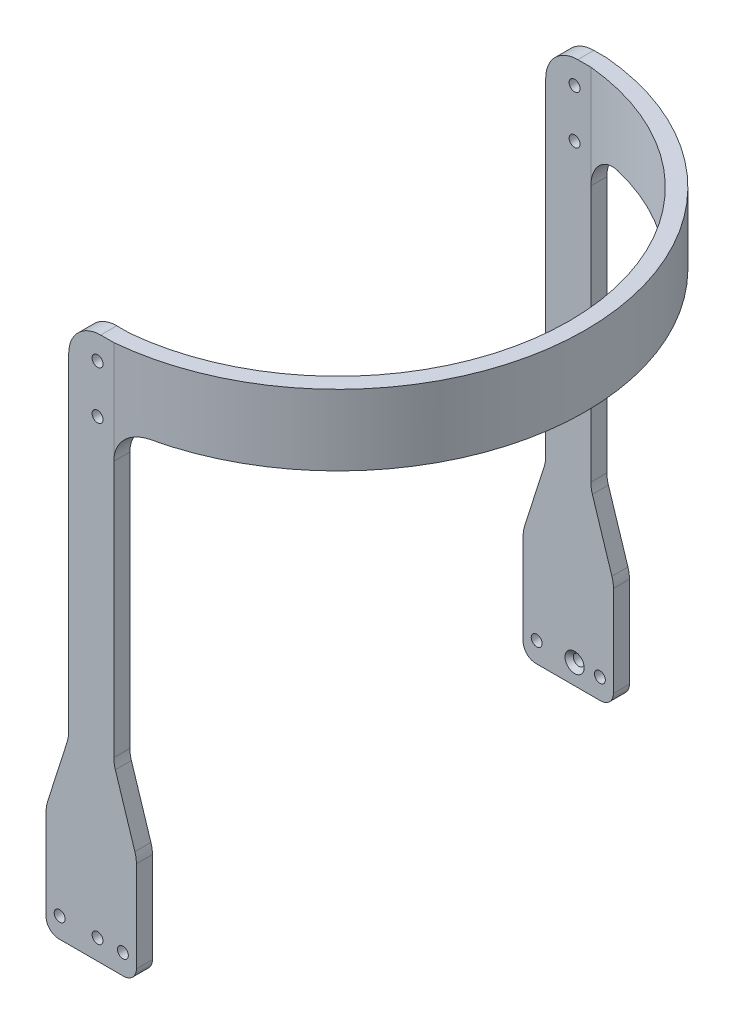
SolidWorks part; units mm, degrees
material "1060 Alloy"
ref_plane "Front Plane" through (0, 0, 0) normal (0, 0, 1) x (1, 0, 0)
ref_plane "Top Plane" through (0, 0, 0) normal (0, 1, 0) x (1, 0, 0)
ref_plane "Right Plane" through (0, 0, 0) normal (1, 0, 0) x (0, 0, -1)
sketch "Sketch1" plane through (0, 0, 0) normal (0, 0, 1) x (1, 0, 0)
  line L0 (0, 0) -> (28.144, 0)
  line L1 (28.144, 0) -> (28.144, 33.908)
  line L2 (28.144, 33.908) -> (21.108, 55.948)
  line L3 (21.108, 55.948) -> (21.108, 169.54)
  line L4 (21.108, 169.54) -> (7.036, 169.54)
  line L5 (7.036, 169.54) -> (7.036, 55.948)
  line L6 (7.036, 55.948) -> (0, 33.908)
  line L7 (0, 33.908) -> (0, 0)
  line L8 (4.2215, 6.332) -> (23.9225, 6.332) construction
  circle A0 centre (4.2215, 6.332) radius 1.7
  circle A1 centre (23.9225, 6.332) radius 1.7
  point P13 (14.072, 6.332)
  point P14 (14.072, 0)
  dimension "D8" = 3.4
  dimension "D1" = 33.908
  dimension "D2" = 55.948
  dimension "D3" = 169.54
  dimension "D4" = 19.701
  dimension "D5" = 28.144
  dimension "D6" = 6.332
  dimension "D7" = 14.072
extrude "Boss-Extrude3" add sketch "Sketch1" along normal blind 5
sketch "Sketch4" plane through (0, 169.54, 0) normal (0, 1, 0) x (1, 0, 0)
  line L0 (21.108, 143.69) -> (21.108, 148.69)
  line L2 (21.108, -5) -> (21.108, 0) construction
  line L3 (21.108, -5) -> (21.108, 0)
  line L5 (21.108, 0) -> (7.036, 0) construction
  line L6 (21.108, 0) -> (7.036, 0) construction
  arc A0 (21.108, -5) -> (21.108, 148.69) centre (14.072, 71.845) ccw
  arc A1 (21.108, 0) -> (21.108, 143.69) centre (14.072, 71.845) ccw
  point P11 (14.072, 0)
  dimension "D1" = 71.845
extrude "Boss-Extrude4" add sketch "Sketch4" against normal blind 22.04
ref_point "Point2"
ref_plane "Plane5" through (23.9225, 0, 0) normal (1, 0, 0) x (0, 0, -1)
ref_plane "Plane4" through (16.0425, 0, 0) normal (1, 0, 0) x (0, 0, -1)
sketch "Sketch5" plane through (16.0425, 0, 0) normal (1, 0, 0) x (0, 0, -1)
  line L0 (-14.8643, 6.332) -> (9.8643, 6.332) construction
  line L1 (-2.5, 6.332) -> (-2.5, 0) construction
  line L2 (-5, 0) -> (0, 0) construction
  line L3 (-5, 6.332) -> (-5, 9.332)
  line L4 (-5, 0) -> (-5, 33.908) construction
  line L6 (0, 0) -> (0, 33.908) construction
  line L7 (0, 8.032) -> (0, 6.332)
  line L8 (0, 6.332) -> (-5, 6.332)
  line L11 (0, 8.032) -> (-3.7, 8.032)
  line L12 (-3.7, 8.032) -> (-5, 9.332)
  dimension "D1" = 6.332
  dimension "D2" = 6
  dimension "D3" = 3.4
  dimension "D4" = 45
revolve "Cut-Revolve1" [suppressed] cut sketch "Sketch5" angle 360 about L0
ref_point "Point1"
ref_plane "Plane3" through (0, 0, -71.845) normal (0, 0, -1) x (-1, 0, 0)
sketch "Sketch6" plane through (0, 0, 5) normal (0, 0, 1) x (1, 0, 0)
  line L0 (16.036, 162.04) -> (16.036, 147.04) construction
  line L1 (7.036, 162.04) -> (21.108, 162.04) construction
  line L2 (21.108, 169.54) -> (7.036, 169.54) construction
  line L3 (7.036, 169.54) -> (7.036, 55.948) construction
  line L4 (21.108, 147.5) -> (21.108, 169.54) construction
  circle A0 centre (16.036, 162.04) radius 1.7
  circle A1 centre (16.036, 147.04) radius 1.7
  point P11 (11.7724, 162.04)
  dimension "D2" = 15
  dimension "D3" = 7.5
  dimension "D4" = 9
extrude "Cut-Extrude1" cut sketch "Sketch6" against normal up to surface (5 mm away) up to face at (14.8538, 74.0324, 0)
mirror "Mirror2" about plane through (0, 0, -71.845) normal (0, 0, -1) of "Boss-Extrude3", "Cut-Extrude1"
fillet "Fillet1" radius 10 4 edges at (7.036, 169.54, -146.19) (7.036, 169.54, 2.5) (21.108, 147.5, -146.19) (21.108, 147.5, 2.5)
fillet "Fillet2" radius 10 8 edges at (21.108, 55.948, 2.5) (28.144, 33.908, 2.5) (0, 33.908, 2.5) (7.036, 55.948, 2.5) (0, 33.908, -146.19) (28.144, 33.908, -146.19) (21.108, 55.948, -146.19) (7.036, 55.948, -146.19)
fillet "Fillet3" radius 4 4 edges at (0, 0, -146.19) (28.144, 0, -146.19) (0, 0, 2.5) (28.144, 0, 2.5)
sketch "Sketch7" plane through (16.0425, 0, 0) normal (1, 0, 0) x (0, 0, -1)
  line L0 (122.4957, 6.332) -> (50122.4957, 6.332) construction
  line L1 (143.69, 6.332) -> (143.69, 9.332)
  line L2 (143.69, 4) -> (143.69, 32.3505) construction
  line L3 (143.69, 9.332) -> (144.99, 8.032)
  line L4 (144.99, 8.032) -> (148.69, 8.032)
  line L5 (148.69, 4) -> (148.69, 32.3505) construction
  line L6 (148.69, 8.032) -> (148.69, 6.332)
  line L7 (148.69, 6.332) -> (143.69, 6.332)
  line L8 (148.69, 0) -> (143.69, 0) construction
  dimension "D1" = 6
  dimension "D2" = 3.4
  dimension "D4" = 6.332
  dimension "D3" = 45
revolve "Cut-Revolve2" cut sketch "Sketch7" angle 360 about L0
mirror "Mirror3" about plane through (0, 0, -71.845) normal (0, 0, -1) of "Cut-Revolve2"
equation "\"B1\"=0.028144"
equation "\"B2\"=0.014072"
equation "\"B3\"=0.066845"
equation "\"H1\"=0.033908"
equation "\"H2\"=0.055948"
equation "\"H3\"=0.147500"
equation "\"H4\"=0.169540"
equation "\"T\"=0.005000"
equation "\"L\"=0.019701"
equation "\"bolt_hole_diameter\"=0.003400"
equation "\"D1@Sketch1\"=\"H1\"*1000"
equation "\"D2@Sketch1\"=\"H2\"*1000"
equation "\"D3@Sketch1\"=\"H4\"*1000"
equation "\"D4@Sketch1\"=\"L\"*1000"
equation "\"D5@Sketch1\"=\"B1\"*1000"
equation "\"D6@Sketch1\"=\"H_holes\"*1000"
equation "\"D7@Sketch1\"=\"B2\"*1000"
equation "\"D8@Sketch1\"=\"bolt_hole_diameter\"*1000"
equation "\"D1@Boss-Extrude3\"=\"T\"*1000"
equation "\"D1@Sketch4\"=\"D_strap\"*1000"
equation "\"D1@Boss-Extrude4\"=(\"H4\"-\"H3\")*1000"
equation "\"spring_arm_hole_pos\"=0.007880"
equation "\"H_holes\"=0.006332"
equation "\"D1@Sketch5\"=\"H_holes\"*1000"
equation "\"spring_arm_hole_max_diam\"=0.006000"
equation "\"spring_arm_hole_min_diam\"=0.003400"
equation "\"arm_hole_head_height\"=0.001650"
equation "\"D1@Plane4\"=\"spring_arm_hole_pos\"*1000"
equation "\"D_strap\"=0.071845"
equation "\"clip_hole_D\"=0.003400"
equation "\"clip_hole_y1\"=0.007500"
equation "\"clip_hole_dist\"=0.015000"
equation "\"pad_t1\"=0.005000"
equation "\"pad_t2\"=0.000000"
equation "\"unpad_L1\"=0.067481"
equation "\"D1@Sketch6\"=\"clip_hole_D\"*1000"
equation "\"D3@Sketch6\"=\"clip_hole_y1\"*1000"
equation "\"D2@Sketch6\"=\"clip_hole_dist\"*1000"
equation "\"D2@Sketch5\"=\"spring_arm_hole_max_diam\"*1000"
equation "\"D3@Sketch5\"=\"spring_arm_hole_min_diam\"*1000"
equation "\"D1@Sketch7\"=\"spring_arm_hole_max_diam\"*1000"
equation "\"D2@Sketch7\"=\"spring_arm_hole_min_diam\"*1000"
equation "\"D4@Sketch7\"=\"H_holes\"*1000"
equation "\"clip_hole_x\"=0.009"
equation "\"D4@Sketch6\"=\"clip_hole_x\"*1000"
